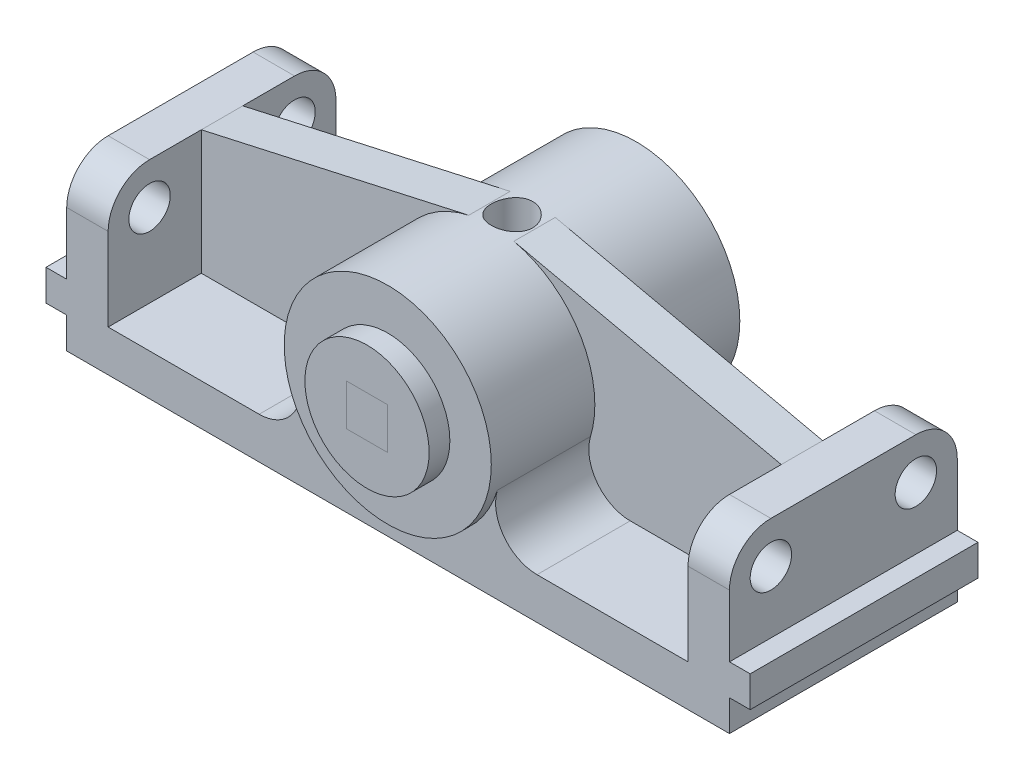
SolidWorks part; units mm, degrees
note: The reader was unsure of these and kept them because the rebuilt part matched: shared geometry of "Sketch7<2>".
material "AISI 1020"
ref_plane "Front Plane" through (0, 0, 0) normal (0, 0, 1) x (1, 0, 0)
ref_plane "Top Plane" through (0, 0, 0) normal (0, 1, 0) x (1, 0, 0)
ref_plane "Right Plane" through (0, 0, 0) normal (1, 0, 0) x (0, 0, -1)
sketch "Sketch1" plane through (0, 0, 0) normal (0, 0, 1) x (1, 0, 0)
  line L0 (0, -38.363) -> (0, 42.9072) construction
  line L1 (-44.3928, 0) -> (43.1693, 0) construction
  circle A0 centre (0, 0) radius 31.75
  dimension "D1" = 63.5
extrude "Boss-Extrude1" add sketch "Sketch1" along normal mid plane 76.2
sketch "Sketch2" plane through (0, 0, 38.1) normal (0, 0, 1) x (1, 0, 0)
  line L0 (-95.25, 12.7) -> (-95.25, -19.05)
  line L1 (-95.25, -19.05) -> (-101.6, -19.05)
  line L2 (-101.6, -19.05) -> (-101.6, -28.575)
  line L3 (-101.6, -28.575) -> (-95.25, -28.575)
  line L4 (-95.25, -28.575) -> (-95.25, -38.1)
  line L5 (-95.25, -38.1) -> (95.25, -38.1)
  line L6 (95.25, -38.1) -> (95.25, -28.575)
  line L7 (95.25, -28.575) -> (101.6, -28.575)
  line L8 (101.6, -28.575) -> (101.6, -19.05)
  line L9 (101.6, -19.05) -> (95.25, -19.05)
  line L10 (95.25, -19.05) -> (95.25, 12.7)
  line L11 (-95.25, 12.7) -> (-82.55, 12.7)
  line L12 (-82.55, 12.7) -> (-82.55, -25.4)
  line L13 (-82.55, -25.4) -> (-42.5971, -25.4)
  line L14 (95.25, 12.7) -> (82.55, 12.7)
  line L15 (82.55, 12.7) -> (82.55, -25.4)
  line L16 (82.55, -25.4) -> (42.5971, -25.4)
  line L17 (0, 65.6124) -> (0, -81.3453) construction
  line L18 (-102.1795, 0) -> (110.8551, 0) construction
  arc A0 (-42.5971, -25.4) -> (-30.4265, -9.0714) centre (-42.5971, -12.7) ccw
  circle A1 centre (0, 0) radius 31.75 construction
  arc A2 (42.5971, -25.4) -> (30.4265, -9.0714) centre (42.5971, -12.7) cw
  arc A3 (-30.4265, -9.0714) -> (30.4265, -9.0714) centre (0, 0) ccw
  point P10 (0, -38.1)
  dimension "D5" = 12.7
  dimension "D1" = 50.8
  dimension "D2" = 12.7
  dimension "D3" = 12.7
  dimension "D4" = 9.525
  dimension "D6" = 6.35
  dimension "D7" = 9.525
  dimension "D8" = 38.1
  dimension "D9" = 203.2
extrude "Boss-Extrude2" [suppressed] add sketch "Sketch2" against normal up to surface (69.85 mm away)
sketch "Sketch4" plane through (0, 0, 0) normal (0, 0, 1) x (1, 0, 0)
  line L0 (-101.6, 12.7) -> (-101.6, -19.05)
  line L1 (-101.6, -19.05) -> (-107.95, -19.05)
  line L2 (-107.95, -19.05) -> (-107.95, -28.575)
  line L3 (-107.95, -28.575) -> (-101.6, -28.575)
  line L4 (-101.6, -28.575) -> (-101.6, -38.1)
  line L5 (-101.6, -38.1) -> (101.6, -38.1)
  line L6 (101.6, -38.1) -> (101.6, -28.575)
  line L7 (101.6, -28.575) -> (107.95, -28.575)
  line L8 (107.95, -28.575) -> (107.95, -19.05)
  line L9 (107.95, -19.05) -> (101.6, -19.05)
  line L10 (101.6, -19.05) -> (101.6, 12.7)
  line L11 (-101.6, 12.7) -> (-88.9, 12.7)
  line L12 (-88.9, 12.7) -> (-88.9, -25.4)
  line L13 (-88.9, -25.4) -> (-42.5971, -25.4)
  line L14 (101.6, 12.7) -> (88.9, 12.7)
  line L15 (88.9, 12.7) -> (88.9, -25.4)
  line L16 (88.9, -25.4) -> (42.5971, -25.4)
  line L17 (-0.1949, 53.3437) -> (-0.1949, -93.614) construction
  line L18 (-106.107, 0) -> (106.9276, 0) construction
  arc A0 (-42.5971, -25.4) -> (-30.4265, -9.0714) centre (-42.5971, -12.7) ccw
  arc A1 (42.5971, -25.4) -> (30.4265, -9.0714) centre (42.5971, -12.7) cw
  circle A3 centre (0, 0) radius 31.75 construction
  arc A5 (-30.4265, -9.0714) -> (30.4265, -9.0714) centre (0, 0) ccw
  point P10 (0, -38.1)
  point P21 (0, 0)
  point P23 (0, 0)
  point P30 (0, 0)
  point P31 (107.95, -23.8125)
  point P32 (0, 0)
  dimension "D9" = 12.7
  dimension "D1" = 12.7
  dimension "D2" = 12.7
  dimension "D3" = 50.8
  dimension "D4" = 9.525
  dimension "D5" = 6.35
  dimension "D6" = 9.525
  dimension "D7" = 38.1
  dimension "D8" = 203.2
extrude "Boss-Extrude3" add sketch "Sketch4" along normal mid plane 69.85
sketch "Sketch5" plane through (0, 0, 0) normal (0, 0, 1) x (1, 0, 0)
  line L0 (-88.9, 12.7) -> (-6.9124, 30.9884)
  circle A0 centre (0, 0) radius 31.75 construction
rib "Rib2" sketch "Sketch5" sketch "Sketch5" thickness 12.7 extrusion direction parallel to sketch draft on no parameters "D1"=12.7
mirror "Mirror1" about plane through (0, 0, 0) normal (1, 0, 0) of "Rib2"
sketch "Sketch6" plane through (0, 0, 0) normal (0, 0, 1) x (1, 0, 0)
  circle A0 centre (0, 0) radius 19.05
  dimension "D1" = 38.1
sketch "Sketch7" plane through (0, 0, 0) normal (0, 0, 1) x (1, 0, 0)
  line L1 (-6.35, -6.35) -> (6.35, -6.35)
  line L2 (-6.35, -6.35) -> (-6.35, 6.35)
  line L3 (-6.35, 6.35) -> (6.35, 6.35)
  line L4 (6.35, -6.35) -> (6.35, 6.35)
  line L5 (-6.35, -6.35) -> (6.35, 6.35) construction
  line L6 (-6.35, 6.35) -> (6.35, -6.35) construction
  point P0 (0, 0)
  point P6 (0, 0)
  dimension "D1" = 12.7
sketch "Sketch10" plane through (0, 0, 0) normal (0, 0, 1) x (1, 0, 0)
  circle A0 centre (0, 0) radius 19.05
  point P2 (0, 0)
  dimension "D1" = 38.1
extrude "Cut-Extrude5" cut sketch "Sketch10" against normal mid plane 88.9
extrude "Boss-Extrude8" add sketch "Sketch6" along normal mid plane 88.9 separate body
extrude "Cut-Extrude6" cut sketch "Sketch7" against normal mid plane 88.9
extrude "Boss-Extrude9" add sketch "Sketch7<2>" along normal mid plane 88.9 separate body
sketch "Sketch7<2>" plane through (0, 0, 0) normal (0, 0, 1) x (1, 0, 0) same geometry as "Sketch7"
sketch "Sketch13" plane through (101.6, 0, 0) normal (1, 0, 0) x (0, 0, -1)
  line L0 (22.225, -55.6225) -> (22.225, 41.8551) construction
  line L1 (0, -63.5935) -> (0, 56.4192) construction
  line L2 (-22.225, -42.3568) -> (-22.225, 55.1208) construction
  line L3 (-63.0301, 0) -> (7.7782, 0) construction
  line L4 (61.0666, 0) -> (7.7782, 0) construction
  line L5 (-34.925, -38.1) -> (34.925, -38.1) construction
  circle A0 centre (-22.225, 0) radius 6.35
  circle A1 centre (22.225, 0) radius 6.35
  point P15 (0, 0)
  point P17 (0, 0)
  point P18 (-20.694, 0)
  point P19 (7.7782, 0)
  dimension "D1" = 12.7
  dimension "D2" = 38.1
  dimension "D3" = 44.45
  dimension "D4" = 22.225
extrude "Cut-Extrude7" cut sketch "Sketch13" against normal up to surface (69.85 mm away)
mirror "Mirror2" about plane through (0, 0, 0) normal (1, 0, 0) of "Cut-Extrude7"
sketch "Sketch14" plane through (101.6, 0, 0) normal (1, 0, 0) x (0, 0, -1)
  line L0 (-34.925, 12.7) -> (34.925, 12.7) construction
  line L1 (-34.925, -19.05) -> (-34.925, 12.7) construction
  line L2 (-34.925, 12.7) -> (-22.225, 12.7)
  line L3 (-34.925, 0) -> (-34.925, 12.7)
  arc A0 (-22.225, 12.7) -> (-34.925, 0) centre (-22.225, 0) ccw
  point P8 (0, 0)
extrude "Cut-Extrude8" cut sketch "Sketch14" against normal up to surface (72.5006 mm away)
mirror "Mirror3" about plane through (0, 0, 0) normal (0, 0, 1) of "Cut-Extrude8"
mirror "Mirror4" about plane through (0, 0, 0) normal (1, 0, 0) of "Mirror3", "Cut-Extrude8"
sketch "Sketch15" plane through (0, 0, 0) normal (0, 1, 0) x (1, 0, 0)
  circle A0 centre (0, 0) radius 6.35
  dimension "D1" = 12.7
extrude "Cut-Extrude9" cut sketch "Sketch15" against normal through all both and the other way through all
